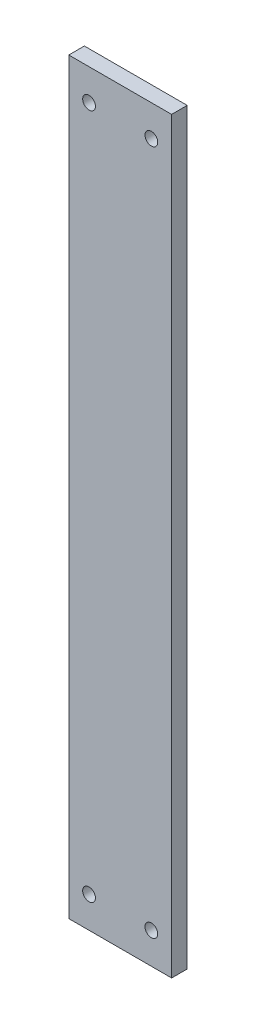
SolidWorks part; units mm, degrees
ref_plane "Plan de face" through (0, 0, 0) normal (0, 0, 1) x (1, 0, 0)
ref_plane "Plan de dessus" through (0, 0, 0) normal (0, 1, 0) x (1, 0, 0)
ref_plane "Plan de droite" through (0, 0, 0) normal (1, 0, 0) x (0, 0, -1)
sketch "Esquisse1" plane through (0, 0, 0) normal (0, 0, 1) x (1, 0, 0)
  line L0 (0, 46.3512) -> (0, -64.121) construction
  line L1 (-76.7381, 0) -> (96.6776, 0) construction
  line L3 (16.5, 120) -> (-16.5, 120) construction
  line L4 (16.5, 120) -> (16.5, -120) construction
  line L5 (16.5, -120) -> (-16.5, -120) construction
  line L6 (-16.5, 120) -> (-16.5, -120) construction
  line L7 (16.5, 120) -> (-16.5, -120) construction
  line L8 (16.5, -120) -> (-16.5, 120) construction
  line L9 (16.5, -120) -> (-16.5, -120)
  line L10 (16.5, -120) -> (16.5, 120)
  line L11 (16.5, 120) -> (-16.5, 120)
  line L12 (-16.5, -120) -> (-16.5, 120)
  line L13 (16.5, -120) -> (-16.5, 120) construction
  line L14 (16.5, 120) -> (-16.5, -120) construction
  circle A0 centre (-10, 110) radius 2.05
  circle A5 centre (-10, -110) radius 2.05
  circle A6 centre (10, -110) radius 2.05
  circle A7 centre (10, 110) radius 2.05
  point P1 (0, 0)
  point P10 (0, 0)
  dimension "D1" = 20
  dimension "D8" = 4.1
  dimension "D3" = 33
  dimension "D4" = 240
  dimension "D5" = 240
  dimension "D6" = 33
  dimension "D7" = 10
extrude "Boss.-Extru.1" add sketch "Esquisse1" along normal blind 5
